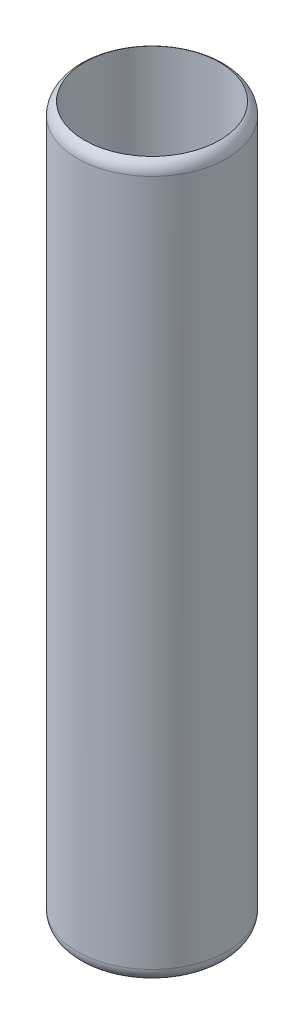
SolidWorks part; units mm, degrees
ref_plane "Alzado" through (0, 0, 0) normal (0, 0, 1) x (1, 0, 0)
ref_plane "Planta" through (0, 0, 0) normal (0, 1, 0) x (1, 0, 0)
ref_plane "Vista lateral" through (0, 0, 0) normal (1, 0, 0) x (0, 0, -1)
sketch "Sketch1" plane through (0, 0, 0) normal (0, 1, 0) x (1, 0, 0)
  circle A0 centre (0, 0) radius 5.25
  dimension "D1" = 10.5
extrude "Boss-Extrude1" add sketch "Sketch1" along normal blind 50
sketch "Sketch2" plane through (0, 50, 0) normal (0, 1, 0) x (1, 0, 0)
  circle A0 centre (0, 0) radius 4.75
  circle A1 centre (0, 0) radius 5.25 construction
  dimension "D1" = 0.5
extrude "Cut-Extrude1" cut sketch "Sketch2" against normal blind 50
fillet "Fillet1" radius 1 2 edges at (0, 0, 5.25) (0, 50, 5.25)
